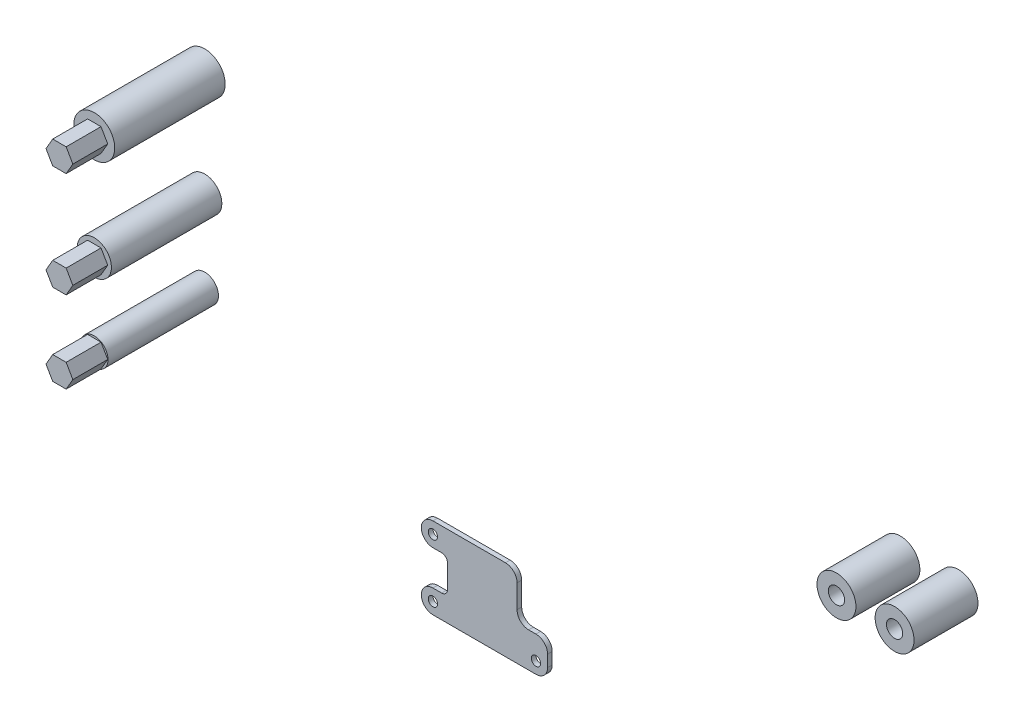
SolidWorks part; units mm, degrees
ref_plane "Front Plane" through (0, 0, 0) normal (0, 0, 1) x (1, 0, 0)
ref_plane "Top Plane" through (0, 0, 0) normal (0, 1, 0) x (1, 0, 0)
ref_plane "Right Plane" through (0, 0, 0) normal (1, 0, 0) x (0, 0, -1)
sketch "Sketch1" plane through (0, 0, 0) normal (0, 0, 1) x (1, 0, 0)
  line L0 (41.5252, 85.2495) -> (55.5016, 85.2495) construction
  line L1 (58.7537, 81.2495) -> (58.7537, 83.2495)
  line L2 (40.5252, 83.2495) -> (39.0252, 83.2495)
  line L3 (39.0252, 79.2495) -> (56.7537, 79.2495)
  line L4 (41.5252, 84.2495) -> (41.5252, 85.2495)
  line L5 (-0.0481, 105.8254) -> (0.9333, 107.5254)
  line L6 (0.9333, 107.5254) -> (-0.0481, 109.2254)
  line L7 (-0.0481, 109.2254) -> (-2.0111, 109.2254)
  line L8 (-2.0111, 109.2254) -> (-2.9926, 107.5254)
  line L9 (-2.9926, 107.5254) -> (-2.0111, 105.8254)
  line L10 (-2.0111, 105.8254) -> (-0.0481, 105.8254)
  line L11 (0.2405, 119.3642) -> (1.5107, 121.5642)
  line L12 (1.5107, 121.5642) -> (0.2405, 123.7642)
  line L13 (0.2405, 123.7642) -> (-2.2998, 123.7642)
  line L14 (-2.2998, 123.7642) -> (-3.57, 121.5642)
  line L15 (-3.57, 121.5642) -> (-2.2998, 119.3642)
  line L16 (-2.2998, 119.3642) -> (0.2405, 119.3642)
  line L17 (0.5292, 136.9341) -> (2.088, 139.6341)
  line L18 (2.088, 139.6341) -> (0.5292, 142.3341)
  line L19 (0.5292, 142.3341) -> (-2.5885, 142.3341)
  line L20 (-2.5885, 142.3341) -> (-4.1473, 139.6341)
  line L21 (-4.1473, 139.6341) -> (-2.5885, 136.9341)
  line L22 (-2.5885, 136.9341) -> (0.5292, 136.9341)
  line L23 (2.088, 139.6341) -> (2.488, 139.6341) construction
  line L24 (1.5107, 121.5642) -> (1.9107, 121.5642) construction
  line L25 (0.9333, 107.5254) -> (1.3333, 107.5254) construction
  line L26 (41.5252, 85.2495) -> (41.5252, 88.2495)
  line L27 (40.5252, 89.2495) -> (39.0252, 89.2495)
  line L28 (39.0252, 93.2495) -> (51.5016, 93.2495)
  line L29 (53.5016, 87.2495) -> (53.5016, 91.2495)
  line L30 (55.5016, 85.2495) -> (56.7537, 85.2495)
  circle A0 centre (39.0252, 81.2495) radius 2
  circle A1 centre (56.7537, 81.2495) radius 2
  circle A2 centre (39.0252, 81.2495) radius 0.8
  circle A3 centre (56.7537, 81.2495) radius 0.8
  arc A4 (58.7537, 83.2495) -> (56.7537, 85.2495) centre (56.7537, 83.2495) ccw
  arc A5 (40.5252, 83.2495) -> (41.5252, 84.2495) centre (40.5252, 84.2495) ccw
  circle A6 centre (-1.0296, 107.5254) radius 1.7 construction
  circle A7 centre (-1.0296, 121.5642) radius 2.2 construction
  circle A8 centre (-1.0296, 139.6341) radius 2.7 construction
  circle A9 centre (-1.0296, 107.5254) radius 2.363
  circle A10 centre (-1.0296, 121.5642) radius 2.9403
  circle A11 centre (-1.0296, 139.6341) radius 3.5177
  circle A12 centre (-1.0296, 139.6341) radius 1.5
  circle A13 centre (-1.0296, 121.5642) radius 1.25
  circle A14 centre (-1.0296, 107.5254) radius 1.05
  circle A15 centre (39.0252, 91.2495) radius 2
  circle A16 centre (39.0252, 91.2495) radius 0.8
  arc A17 (41.5252, 88.2495) -> (40.5252, 89.2495) centre (40.5252, 88.2495) ccw
  arc A18 (53.5016, 91.2495) -> (51.5016, 93.2495) centre (51.5016, 91.2495) ccw
  arc A19 (55.5016, 85.2495) -> (53.5016, 87.2495) centre (55.5016, 87.2495) cw
  circle B0 centre (78.6519, 127.0575) radius 1.4
  circle B1 centre (78.6519, 127.0575) radius 3.35
  circle B2 centre (78.736, 101.9939) radius 0.85
  circle B3 centre (78.736, 101.9939) radius 2.9
  circle B4 centre (78.736, 114.8621) radius 1.1
  circle B5 centre (78.736, 114.8621) radius 2.7
  circle B6 centre (88.6519, 127.0575) radius 1.4
  circle B7 centre (88.6519, 127.0575) radius 3.35
  circle B8 centre (98.6519, 127.0575) radius 1.4
  circle B9 centre (98.6519, 127.0575) radius 3.35
  circle B10 centre (108.6519, 127.0575) radius 1.4
  circle B11 centre (108.6519, 127.0575) radius 3.35
  circle B12 centre (118.6519, 127.0575) radius 1.4
  circle B13 centre (118.6519, 127.0575) radius 3.35
  circle B14 centre (128.6519, 127.0575) radius 1.4
  circle B15 centre (128.6519, 127.0575) radius 3.35
  circle B16 centre (88.736, 101.9939) radius 0.85
  circle B17 centre (88.736, 101.9939) radius 2.9
  circle B18 centre (98.736, 101.9939) radius 0.85
  circle B19 centre (98.736, 101.9939) radius 2.9
  circle B20 centre (108.736, 101.9939) radius 0.85
  circle B21 centre (108.736, 101.9939) radius 2.9
  circle B22 centre (88.736, 114.8621) radius 1.1
  circle B23 centre (88.736, 114.8621) radius 2.7
  circle B24 centre (76.8787, 139.9756) radius 1.6
  circle B25 centre (76.8787, 139.9756) radius 4
  circle B26 centre (86.8787, 139.9756) radius 1.6
  circle B27 centre (86.8787, 139.9756) radius 4
  dimension "D1" = 4
  dimension "D2" = 1.6
  dimension "D4" = 2
  dimension "D6" = 1
  dimension "D11" = 3
  dimension "D12" = 2.5
  dimension "D13" = 2.1
  dimension "D18" = 4
  dimension "D19" = 1.6
  dimension "D20" = 1
  dimension "D21" = 2
  dimension "D22" = 2
  dimension "D26" = 2
  dimension "D3" = 4
  dimension "D5" = 2.5
  dimension "D7" = 17.7284
  dimension "D8" = 3.4
  dimension "D9" = 5.4
  dimension "D10" = 4.4
  dimension "D14" = 0.4
  dimension "D15" = 0.4
  dimension "D16" = 0.4
  dimension "D17" = 10
  dimension "D23" = 6
  dimension "D24" = 4
  dimension "D25" = 2
sketch_block_instance "M2.5 spacer-10"
sketch_block "M2.5 spacer" parameters "D1"=2.8, "D3"=6.7, "D4"=2.7, "D2"=4.7
sketch_block_instance "M1.6 spacer-11"
sketch_block "M1.6 spacer" parameters "D1"=1.7, "D3"=5.8, "D4"=1.8, "D2"=3.8
sketch_block_instance "M2 spacer-4"
sketch_block "M2 spacer" parameters "D1"=2.2, "D3"=1, "D4"=2.2, "D2"=3.8
sketch_block_instance "M2.5 spacer-15"
sketch_block_instance "M2.5 spacer-16"
sketch_block_instance "M2.5 spacer-17"
sketch_block_instance "M2.5 spacer-18"
sketch_block_instance "M2.5 spacer-19"
sketch_block_instance "M1.6 spacer-14"
sketch_block_instance "M1.6 spacer-15"
sketch_block_instance "M1.6 spacer-16"
sketch_block_instance "M2 spacer-6"
sketch_block_instance "M3 spacer-1"
sketch_block "M3 spacer" parameters "D1"=3.2, "D2"=8, "D3"=5.6
sketch_block_instance "M3 spacer-2"
extrude "Boss-Extrude1" add sketch "Sketch1" along normal blind 4 contours A11 L22 L21 L20 L19 L18 L17 | A10 L16 L15 L14 L13 L12 L11 | A9 L10 L9 L8 L7 L6 L5 region at (-3.3258, 107.5254, 0) region at (-3.8868, 121.5642, 0) region at (-4.4478, 139.6341, 0)
extrude "Boss-Extrude2" add sketch "Sketch1<3>" along normal blind 15 from surface contours L9 L10 L5 L6 L7 L8 A14 | A9 L10 L9 L8 L7 L6 L5 | A10 L16 L15 L14 L13 L12 L11 | L15 L16 L11 L12 L13 L14 A13 | A11 L22 L21 L20 L19 L18 L17 | L21 L22 L17 L18 L19 L20 A12 region at (-1.0296, 105.8773, 0) region at (-1.0296, 119.4314, 0) region at (-1.0296, 137.0166, 0) region at (-3.3258, 107.5254, 0) region at (-3.8868, 121.5642, 0) region at (-4.4478, 139.6341, 0) starting at face at (-1.0296, 139.6341, 4)
sketch "Sketch1<3>" plane through (0, 0, 0) normal (0, 0, 1) x (1, 0, 0) same geometry as "Sketch1"
sketch "Sketch2" plane through (0, 0, 19) normal (0, 0, 1) x (1, 0, 0)
  line B0 (0.1251, 137.6341) -> (1.2798, 139.6341)
  line B1 (1.2798, 139.6341) -> (0.1251, 141.6341)
  line B2 (0.1251, 141.6341) -> (-2.1843, 141.6341)
  line B3 (-2.1843, 141.6341) -> (-3.339, 139.6341)
  line B4 (-3.339, 139.6341) -> (-2.1843, 137.6341)
  line B5 (-2.1843, 137.6341) -> (0.1251, 137.6341)
  circle B6 centre (-1.0296, 139.6341) radius 2 construction
  line B7 (0.1251, 119.5642) -> (1.2798, 121.5642)
  line B8 (1.2798, 121.5642) -> (0.1251, 123.5642)
  line B9 (0.1251, 123.5642) -> (-2.1843, 123.5642)
  line B10 (-2.1843, 123.5642) -> (-3.339, 121.5642)
  line B11 (-3.339, 121.5642) -> (-2.1843, 119.5642)
  line B12 (-2.1843, 119.5642) -> (0.1251, 119.5642)
  circle B13 centre (-1.0296, 121.5642) radius 2 construction
  line B14 (0.1251, 105.5254) -> (1.2798, 107.5254)
  line B15 (1.2798, 107.5254) -> (0.1251, 109.5254)
  line B16 (0.1251, 109.5254) -> (-2.1843, 109.5254)
  line B17 (-2.1843, 109.5254) -> (-3.339, 107.5254)
  line B18 (-3.339, 107.5254) -> (-2.1843, 105.5254)
  line B19 (-2.1843, 105.5254) -> (0.1251, 105.5254)
  circle B20 centre (-1.0296, 107.5254) radius 2 construction
sketch_block_instance "T4-hex-1"
sketch_block "T4-hex" parameters "D1"=4
sketch_block_instance "T4-hex-2"
sketch_block_instance "T4-hex-3"
extrude "Boss-Extrude3" add sketch "Sketch2" along normal blind 6
chamfer "Chamfer1" distance 1 angle 60 1 edges at (0.0204, 107.5254, 19) first distance on face at (0.0204, 107.5254, 19)
chamfer "Chamfer2" distance 1.2 angle 60 1 edges at (0.2204, 121.5642, 19) first distance on face at (0.2204, 121.5642, 19)
chamfer "Chamfer3" distance 1.4 angle 60 1 edges at (0.4704, 139.6341, 19) first distance on face at (0.4704, 139.6341, 19)
extrude "Boss-Extrude4" add sketch "Sketch1<5>" along normal blind 0.8 separate body contours L30 A19 L29 A18 L28 A15 L27 A17 L26 L4 A5 L2 A0 L3 A1 L1 A4 | A0 A2 | A1 A3 | A15 A16 region at (47.9603, 85.9255, 0) region at (58.1279, 79.8753, 0) region at (37.0818, 81.2495, 0) region at (40.3994, 92.6237, 0)
sketch "Sketch1<5>" plane through (0, 0, 0) normal (0, 0, 1) x (1, 0, 0) same geometry as "Sketch1"
extrude "Boss-Extrude5" add sketch "Sketch1<7>" along normal blind 11 separate body contours B15 B14 | B13 B12 region at (115.3966, 127.0575, 0) region at (125.3966, 127.0575, 0)
sketch "Sketch1<7>" plane through (0, 0, 0) normal (0, 0, 1) x (1, 0, 0) same geometry as "Sketch1"
